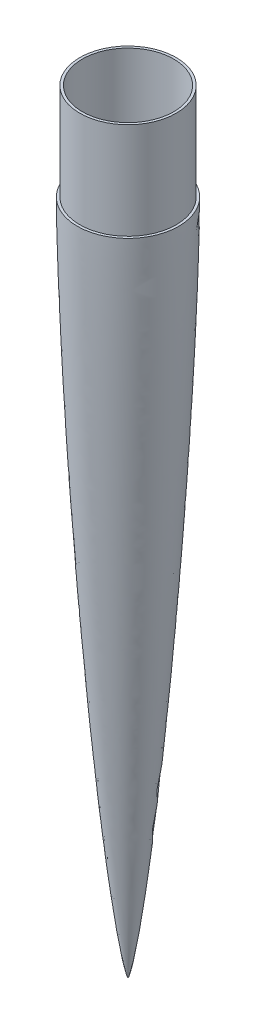
SolidWorks part; units mm, degrees
ref_plane "Front Plane" through (0, 0, 0) normal (0, 0, 1) x (1, 0, 0)
ref_plane "Top Plane" through (0, 0, 0) normal (0, 1, 0) x (1, 0, 0)
ref_plane "Right Plane" through (0, 0, 0) normal (1, 0, 0) x (0, 0, -1)
sketch "Sketch1" plane through (0, 0, 0) normal (0, 0, 1) x (1, 0, 0)
  line L0 (-60, 0) -> (-57.03, 0)
  line L1 (0, -789.4472) -> (0, -579.6585) construction
  line L4 (0, -800) -> (0, -789.4472)
  line L5 (0, -800) -> (223.4856, -38.024) construction
  line L6 (0, -789.4472) -> (220.6357, -37.1881) construction
  line L7 (-54.06, 0) -> (-54.9769, -95.2674)
  line L9 (-57.03, 0) -> (-57.03, 114.3)
  line L10 (-57.03, 114.3) -> (-54.06, 114.3)
  line L11 (-54.06, 0) -> (-54.06, 114.3)
  spline S0 degree 1 poles (-57.03, 0) (0, -789.4472) knots 0 0 1 1 construction
  spline S4 degree 3 poles (-60, 0) (-60, -0.8013) (-59.9929, -2.1349) (-59.9805, -4.3959) (-59.9625, -6.5446) (-59.9428, -8.7499) (-59.9191, -10.9255) (-59.8941, -13.1168) (-59.8662, -15.2995) (-59.8366, -17.4868) (-59.8051, -19.6717) (-59.7715, -21.8581) (-59.7369, -24.0435) (-59.7, -26.2297) (-59.662, -28.4153) (-59.6225, -30.6013) (-59.5815, -32.787) (-59.539, -34.9727) (-59.4956, -37.1584) (-59.4503, -39.3441) (-59.4045, -41.5301) (-59.3568, -43.7158) (-59.3086, -45.9018) (-59.2586, -48.0875) (-59.2081, -50.2732) (-59.1558, -52.4589) (-59.1035, -54.6446) (-59.0483, -56.8306) (-58.9943, -59.0163) (-58.9382, -61.2023) (-58.8811, -63.388) (-58.8234, -65.574) (-58.7644, -67.7597) (-58.7047, -69.9454) (-58.6439, -72.1311) (-58.5823, -74.3168) (-58.5197, -76.5028) (-58.4565, -78.6885) (-58.3921, -80.8745) (-58.3271, -83.0602) (-58.2612, -85.246) (-58.1942, -87.4317) (-58.1273, -89.6174) (-58.0586, -91.8033) (-57.9893, -93.9889) (-57.9195, -96.175) (-57.8486, -98.3607) (-57.7772, -100.5467) (-57.7051, -102.7324) (-57.6078, -105.6469) (-57.5088, -108.561) (-57.4086, -111.4755) (-57.3329, -113.6612) (-57.256, -115.8472) (-57.179, -118.0329) (-57.1007, -120.2185) (-57.022, -122.4042) (-56.9429, -124.5899) (-56.8623, -126.7759) (-56.7822, -128.9616) (-56.6997, -131.1476) (-56.6183, -133.3334) (-56.5355, -135.5194) (-56.4521, -137.7051) (-56.368, -139.8907) (-56.2833, -142.0764) (-56.198, -144.2621) (-56.1119, -146.4481) (-56.0255, -148.6338) (-55.9379, -150.8198) (-55.8503, -153.0055) (-55.7613, -155.1912) (-55.6431, -158.1054) (-55.5227, -161.0199) (-55.4016, -163.9343) (-55.3099, -166.1203) (-55.2181, -168.306) (-55.1248, -170.492) (-55.0321, -172.6777) (-54.9376, -174.8634) (-54.8436, -177.0491) (-54.748, -179.2348) (-54.6526, -181.4208) (-54.5565, -183.6065) (-54.4595, -185.7925) (-54.3622, -187.9782) (-54.2643, -190.1639) (-54.1656, -192.3496) (-54.0666, -194.5353) (-53.9668, -196.7213) (-53.8667, -198.907) (-53.7659, -201.093) (-53.6647, -203.2787) (-53.5626, -205.4647) (-53.4602, -207.6504) (-53.3575, -209.8361) (-53.2538, -212.0218) (-53.1499, -214.2075) (-53.0452, -216.3935) (-52.94, -218.5792) (-52.8343, -220.7652) (-52.728, -222.9509) (-52.6216, -225.1366) (-52.5138, -227.3223) (-52.4067, -229.508) (-52.2972, -231.694) (-52.1899, -233.8797) (-52.0791, -236.0657) (-51.9699, -238.2514) (-51.859, -240.4374) (-51.7483, -242.6231) (-51.6367, -244.8088) (-51.5246, -246.9945) (-51.4123, -249.1802) (-51.2989, -251.3662) (-51.1858, -253.5519) (-51.0711, -255.7379) (-50.9569, -257.9236) (-50.8414, -260.1093) (-50.7262, -262.295) (-50.6098, -264.4807) (-50.4931, -266.6667) (-50.3761, -268.8524) (-50.2582, -271.0384) (-50.1402, -273.2241) (-50.0213, -275.41) (-49.9023, -277.5957) (-49.7825, -279.7813) (-49.6622, -281.9672) (-49.5416, -284.1528) (-49.4202, -286.3389) (-49.2988, -288.5246) (-49.1758, -290.7106) (-49.0546, -292.8963) (-48.9296, -295.0819) (-48.807, -297.2677) (-48.6822, -299.4533) (-48.5576, -301.6394) (-48.4324, -303.8251) (-48.3066, -306.0111) (-48.1383, -308.9256) (-47.9688, -311.84) (-47.7987, -314.7542) (-47.6703, -316.9398) (-47.5417, -319.1255) (-47.4122, -321.3116) (-47.2825, -323.4973) (-47.1525, -325.6833) (-47.0216, -327.869) (-46.8905, -330.0547) (-46.7584, -332.2403) (-46.6266, -334.426) (-46.4937, -336.612) (-46.3605, -338.7977) (-46.2267, -340.9838) (-46.0927, -343.1695) (-45.9577, -345.3554) (-45.8228, -347.5411) (-45.6865, -349.7267) (-45.5513, -351.9126) (-45.414, -354.0982) (-45.2766, -356.2842) (-45.1391, -358.4699) (-45.0008, -360.656) (-44.862, -362.8417) (-44.7229, -365.0274) (-44.583, -367.213) (-44.4431, -369.3987) (-44.3019, -371.5847) (-44.1609, -373.7704) (-44.0192, -375.9564) (-43.8768, -378.1421) (-43.7342, -380.3279) (-43.5909, -382.5136) (-43.4471, -384.6993) (-43.3028, -386.8852) (-43.158, -389.0709) (-43.0129, -391.2569) (-42.8669, -393.4426) (-42.7207, -395.6286) (-42.5738, -397.8143) (-42.4265, -400) (-42.2786, -402.1857) (-42.1303, -404.3714) (-41.9816, -406.5574) (-41.8317, -408.7431) (-41.6828, -410.9292) (-41.5315, -413.1148) (-41.3304, -416.0293) (-41.1281, -418.9434) (-40.9247, -421.8579) (-40.7717, -424.0436) (-40.6181, -426.2296) (-40.464, -428.4153) (-40.3092, -430.6013) (-40.1543, -432.787) (-39.9986, -434.9727) (-39.8422, -437.1584) (-39.6858, -439.3441) (-39.5281, -441.5301) (-39.3707, -443.7158) (-39.2119, -445.9018) (-39.0534, -448.0875) (-38.8936, -450.2733) (-38.7337, -452.459) (-38.5732, -454.6447) (-38.4121, -456.8306) (-38.2506, -459.0163) (-38.0881, -461.2023) (-37.9257, -463.388) (-37.762, -465.574) (-37.598, -467.7597) (-37.4343, -469.9454) (-37.2688, -472.131) (-37.1036, -474.3168) (-36.9373, -476.5028) (-36.7707, -478.6885) (-36.6033, -480.8745) (-36.4356, -483.0602) (-36.2672, -485.2459) (-36.098, -487.4316) (-35.9287, -489.6173) (-35.7583, -491.8033) (-35.5877, -493.989) (-35.4164, -496.175) (-35.2444, -498.3607) (-35.072, -500.5467) (-34.8989, -502.7324) (-34.6672, -505.6469) (-34.4346, -508.5611) (-34.2003, -511.4755) (-34.0243, -513.6612) (-33.8474, -515.8471) (-33.6708, -518.0329) (-33.4917, -520.2187) (-33.3136, -522.4044) (-33.1342, -524.5901) (-32.9542, -526.7759) (-32.774, -528.9617) (-32.5924, -531.1477) (-32.4109, -533.3334) (-32.2282, -535.5194) (-32.0451, -537.7051) (-31.8612, -539.8907) (-31.6767, -542.0764) (-31.492, -544.2622) (-31.3059, -546.4482) (-31.1193, -548.6338) (-30.9323, -550.8199) (-30.7445, -553.0056) (-30.556, -555.1913) (-30.3665, -557.3769) (-30.1772, -559.5627) (-29.9857, -561.7486) (-29.7949, -563.9344) (-29.6027, -566.1204) (-29.4099, -568.3061) (-29.2165, -570.4921) (-29.0221, -572.6778) (-28.8273, -574.8635) (-28.6313, -577.0491) (-28.4352, -579.2348) (-28.2375, -581.4208) (-28.0398, -583.6065) (-27.8408, -585.7925) (-27.6414, -587.9782) (-27.4411, -590.1639) (-27.2398, -592.3496) (-27.038, -594.5353) (-26.8348, -596.7213) (-26.6319, -598.9071) (-26.4266, -601.093) (-26.2222, -603.2788) (-26.0156, -605.4647) (-25.8089, -607.6504) (-25.601, -609.8361) (-25.3924, -612.0218) (-25.1829, -614.2075) (-24.9723, -616.3935) (-24.7612, -618.5792) (-24.5487, -620.7652) (-24.3356, -622.9509) (-24.1217, -625.1367) (-23.9063, -627.3223) (-23.6908, -629.508) (-23.4731, -631.694) (-23.2563, -633.8798) (-23.0363, -636.0657) (-22.8168, -638.2515) (-22.5956, -640.4375) (-22.3738, -642.6232) (-22.1506, -644.8088) (-21.9265, -646.9945) (-21.7017, -649.1802) (-21.4749, -651.3662) (-21.248, -653.5519) (-21.019, -655.7379) (-20.7898, -657.9237) (-20.4816, -660.8382) (-20.1719, -663.7524) (-19.8593, -666.6668) (-19.6238, -668.8524) (-19.3867, -671.0384) (-19.1486, -673.2242) (-18.9089, -675.4102) (-18.6684, -677.5959) (-18.426, -679.7815) (-18.1825, -681.9672) (-17.9376, -684.1529) (-17.6911, -686.3389) (-17.3605, -689.2535) (-17.0271, -692.168) (-16.6903, -695.082) (-16.4364, -697.2677) (-16.1806, -699.4534) (-15.9232, -701.6394) (-15.6637, -703.8251) (-15.4033, -706.0112) (-15.1403, -708.1968) (-14.7877, -711.1115) (-14.431, -714.0256) (-14.0705, -716.94) (-13.7976, -719.1256) (-13.5232, -721.3117) (-13.2464, -723.4974) (-12.967, -725.6834) (-12.6855, -727.8691) (-12.4017, -730.0548) (-12.1149, -732.2404) (-11.8261, -734.4262) (-11.5335, -736.6122) (-11.2396, -738.798) (-10.9412, -740.9839) (-10.641, -743.1697) (-10.3368, -745.3557) (-10.0294, -747.5414) (-9.7189, -749.7271) (-9.404, -751.9128) (-9.0856, -754.0985) (-8.7627, -756.2845) (-8.4361, -758.4703) (-8.1038, -760.6562) (-7.7675, -762.842) (-7.4253, -765.0277) (-7.0775, -767.2135) (-6.7236, -769.3992) (-6.3629, -771.5853) (-5.9952, -773.7711) (-5.6185, -775.9572) (-5.234, -778.143) (-4.8375, -780.3289) (-4.4328, -782.5152) (-4.0092, -784.7007) (-3.5793, -786.8876) (-3.1137, -789.0724) (-2.656, -791.2623) (-2.1075, -793.4442) (-1.6286, -795.6455) (-0.8407, -797.8415) (-0.5824, -799.3519) (0, -800) knots 0 0 0 0 0.002721 0.005444 0.008165 0.010888 0.013609 0.016332 0.019054 0.021775 0.024498 0.02722 0.029942 0.032664 0.035387 0.038109 0.040832 0.043554 0.046275 0.048999 0.051721 0.054444 0.057166 0.059889 0.062611 0.065333 0.068056 0.070778 0.073502 0.076224 0.078948 0.08167 0.084393 0.087116 0.089838 0.092562 0.095284 0.098008 0.10073 0.103454 0.106176 0.108899 0.111623 0.114345 0.117069 0.119792 0.122516 0.125239 0.127963 0.130686 0.136133 0.138855 0.14158 0.144303 0.147027 0.14975 0.152473 0.155197 0.15792 0.160645 0.163368 0.166092 0.168816 0.17154 0.174263 0.176987 0.179711 0.182435 0.185159 0.187883 0.190608 0.193331 0.196055 0.201503 0.204228 0.206952 0.209677 0.212401 0.215126 0.217849 0.220573 0.223298 0.226022 0.228747 0.231471 0.234197 0.236921 0.239645 0.24237 0.245094 0.247819 0.250544 0.253269 0.255993 0.258719 0.261443 0.264168 0.266893 0.269618 0.272343 0.275068 0.277794 0.280518 0.283243 0.285968 0.288693 0.291419 0.294144 0.29687 0.299594 0.30232 0.305045 0.30777 0.310496 0.313221 0.315947 0.318672 0.321399 0.324124 0.326849 0.329575 0.332301 0.335027 0.337752 0.340479 0.343204 0.34593 0.348656 0.351381 0.354108 0.356834 0.35956 0.362286 0.365013 0.367738 0.370464 0.373191 0.375917 0.378644 0.381369 0.384096 0.389549 0.392275 0.395001 0.397729 0.400455 0.403182 0.405908 0.408636 0.411362 0.414088 0.416815 0.419542 0.422269 0.424996 0.427723 0.43045 0.433177 0.435904 0.438631 0.441359 0.444085 0.446813 0.44954 0.452268 0.454995 0.457722 0.46045 0.463177 0.465905 0.468632 0.47136 0.474087 0.476815 0.479543 0.48227 0.484999 0.487726 0.490454 0.493182 0.495911 0.498638 0.501366 0.504094 0.506822 0.509551 0.512278 0.515007 0.517735 0.523192 0.52592 0.528649 0.531377 0.534107 0.536835 0.539564 0.542292 0.54502 0.54775 0.550478 0.553208 0.555936 0.558666 0.561395 0.564124 0.566853 0.569582 0.572312 0.575041 0.577771 0.580499 0.58323 0.585959 0.588688 0.591418 0.594147 0.596878 0.599607 0.602337 0.605067 0.607796 0.610527 0.613256 0.615987 0.618717 0.621448 0.624178 0.626909 0.629639 0.6351 0.63783 0.640561 0.643291 0.646023 0.648753 0.651484 0.654215 0.656946 0.659677 0.662408 0.66514 0.667871 0.670603 0.673334 0.676065 0.678797 0.681528 0.684261 0.686992 0.689724 0.692456 0.695187 0.69792 0.700652 0.703385 0.706116 0.708849 0.711581 0.714315 0.717047 0.719779 0.722512 0.725245 0.727979 0.730711 0.733445 0.736178 0.73891 0.741645 0.744378 0.747112 0.749845 0.75258 0.755313 0.758048 0.760781 0.763515 0.76625 0.768984 0.771719 0.774453 0.777189 0.779923 0.782657 0.785393 0.788128 0.790864 0.793599 0.796335 0.79907 0.801807 0.804542 0.807278 0.810015 0.81275 0.815488 0.818224 0.820961 0.823698 0.829172 0.831909 0.834648 0.837385 0.840123 0.842861 0.8456 0.848338 0.851076 0.853816 0.856554 0.859294 0.864774 0.867513 0.870253 0.872994 0.875734 0.878475 0.881216 0.883958 0.886699 0.892184 0.894926 0.897669 0.900412 0.903156 0.9059 0.908645 0.911389 0.914134 0.91688 0.919625 0.922373 0.925119 0.927867 0.930615 0.933364 0.936113 0.938862 0.941613 0.944364 0.947117 0.949869 0.952624 0.955378 0.958134 0.960892 0.96365 0.966411 0.969172 0.971937 0.974702 0.977471 0.980243 0.983018 0.985799 0.988585 0.991381 0.994189 0.997025 1 1 1 1
  spline S6 degree 3 poles (-57.03, 0) (-57.03, -0.2667) (-57.0291, -0.8152) (-57.026, -1.5473) (-57.0219, -2.2906) (-57.0163, -3.3241) (-57.0082, -4.6397) (-56.9915, -6.6698) (-56.9677, -9.2654) (-56.8986, -15.4333) (-56.703, -28.8497) (-56.2787, -49.464) (-55.6328, -74.2142) (-54.6204, -107.2097) (-53.1137, -148.4503) (-50.276, -214.4221) (-46.0241, -296.8587) (-40.9297, -379.2464) (-36.3367, -445.1211) (-32.618, -494.507) (-28.6013, -543.8673) (-24.2469, -593.1958) (-19.4892, -642.482) (-15.0964, -683.5036) (-11.2041, -716.2659) (-8.031, -740.7984) (-5.0833, -761.1793) (-2.3992, -777.4138) (-0.8567, -785.4439) (0, -789.4472) knots 0 0 0 0 0.000964 0.001928 0.002892 0.003856 0.005784 0.007711 0.011567 0.015423 0.030846 0.061692 0.092538 0.123384 0.185075 0.246767 0.370151 0.493535 0.555226 0.616918 0.67861 0.740302 0.801994 0.863686 0.894531 0.925377 0.956223 0.971646 0.987069 0.987069 0.987069 0.987069 only from (-54.9769, -95.2674) to (0, -789.4472)
  dimension "D1" = 114.3
  dimension "D3" = 2.97
  dimension "D2" = 2.97
revolve "Revolve2" add sketch "Sketch1" angle 360 about L1
